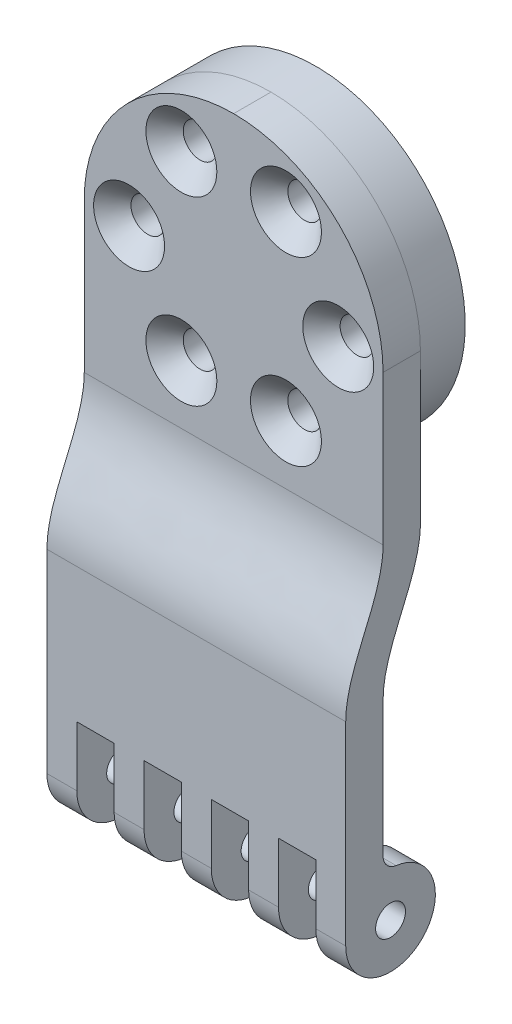
SolidWorks part; units mm, degrees
other "Markup1"
sketch "Sketch13" plane through (20, -53, 11) normal (0.0614, -0.6805, 0.7302) x (0.9699, -0.1321, -0.2046)
ref_plane "Front Plane" through (0, 0, 0) normal (0, 0, 1) x (1, 0, 0)
ref_plane "Top Plane" through (0, 0, 0) normal (0, 1, 0) x (1, 0, 0)
ref_plane "Right Plane" through (0, 0, 0) normal (1, 0, 0) x (0, 0, -1)
sketch "Sketch7" plane through (0, 0, 0) normal (0, 0, 1) x (1, 0, 0)
  line L1 (-20, 20) -> (20, 20)
  line L2 (-20, 20) -> (-20, -20)
  line L3 (-20, -20) -> (20, -20)
  line L4 (20, 20) -> (20, -20)
  line L5 (-20, 20) -> (20, -20) construction
  line L6 (-20, -20) -> (20, 20) construction
  point P0 (0, 0)
extrude "Boss-Extrude1" add sketch "Sketch7" along normal blind 11
ref_plane "Plane2" through (0, -21.4103, 5.7369) normal (0, -0.9659, 0.2588) x (1, 0, 0)
sketch "Sketch8" plane through (0, -20, 2.0782) normal (0, -1, 0) x (1, 0, 0)
  line L0 (20, 8.9218) -> (20, -2.0782) construction
  line L1 (-20, 8.9218) -> (20, 8.9218)
  line L2 (-20, 8.9218) -> (-20, 3.9218)
  line L3 (-20, 3.9218) -> (20, 3.9218)
  line L4 (20, 8.9218) -> (20, 3.9218)
  line L5 (0, 3.9218) -> (0, 8.9218) construction
  line L6 (-20, 6.4218) -> (20, 6.4218) construction
  line L7 (-20, -2.0782) -> (20, -2.0782) construction
  point P764 (0, 6.4218)
  dimension "D1" = 6
ref_plane "Plane4" through (0, -38, 0) normal (0, -1, 0) x (-1, 0, 0)
sketch "Sketch19" plane through (0, -38, 0) normal (0, -1, 0) x (-1, 0, 0)
  line L0 (20, -11) -> (20, 0) construction
  line L1 (20, -16) -> (-20, -16)
  line L2 (20, -16) -> (20, -11)
  line L3 (20, -11) -> (-20, -11)
  line L4 (-20, -16) -> (-20, -11)
  line L5 (20, -16) -> (-20, -11) construction
  line L6 (20, -11) -> (-20, -16) construction
  line L7 (-20, -11) -> (-20, 0) construction
  line L8 (20, -11) -> (-20, -11) construction
  point P4 (0, -13.5)
  dimension "D1" = 5
  dimension "D2" = 5
loft "Loft1" add profiles "Sketch19", "Sketch8" start constraint normal to profile start tangent length 1 end constraint normal to profile end tangent length 1 connector at (-20, -38, 16) connector at (-20, -20, 11)
sketch "Sketch16" plane through (0, 0, 0) normal (0, 0, -1) x (-1, 0, 0)
  line L1 (24.5131, 32.6211) -> (-24.5131, 32.6211)
  line L2 (24.5131, 32.6211) -> (24.5131, -32.6211)
  line L3 (24.5131, -32.6211) -> (-24.5131, -32.6211)
  line L4 (-24.5131, 32.6211) -> (-24.5131, -32.6211)
  line L5 (24.5131, 32.6211) -> (-24.5131, -32.6211) construction
  line L6 (24.5131, -32.6211) -> (-24.5131, 32.6211) construction
  circle A0 centre (0, 0) radius 20
extrude "Cut-Extrude3" cut sketch "Sketch16" against normal blind 6
ref_plane "Plane3" [suppressed] through (0, -56, 0) normal (0, -1, 0) x (-1, 0, 0)
sketch "Sketch17" plane through (0, -38, 0) normal (0, -1, 0) x (-1, 0, 0)
  line L1 (20, -16) -> (-20, -16)
  line L2 (20, -16) -> (20, -11)
  line L3 (20, -11) -> (-20, -11)
  line L4 (-20, -16) -> (-20, -11)
  line L5 (20, -16) -> (-20, -11) construction
  line L6 (20, -11) -> (-20, -16) construction
  line L10 (-20, -16) -> (20, -16) construction
  line L11 (-20, -6) -> (-20, -11) construction
  line L12 (20, -11) -> (20, -6) construction
  point P4 (0, -13.5)
  dimension "D1" = 5
extrude "Boss-Extrude5" add sketch "Sketch17" along normal blind 18
sketch "Sketch10" plane through (0, 0, 11) normal (0, 0, 1) x (1, 0, 0)
  circle A0 centre (-7.0001, 12.1244) radius 2.25
  circle A1 centre (6.9999, 12.1244) radius 2.25
  circle A2 centre (13.9999, 0.0001) radius 2.25
  circle A3 centre (6.9999, -12.1243) radius 2.25
  circle A4 centre (-7.0001, -12.1243) radius 2.25
  circle A5 centre (-14.0001, 0.0001) radius 2.25
  point P0 (0, 0)
  point P1 (0.0025, 0.0011)
  dimension "D4" = 4.5
extrude "Cut-Extrude1" cut sketch "Sketch10" against normal blind 25
sketch "Sketch11" plane through (0, -56, -3.473) normal (0, 1, 0) x (1, 0, 0)
  line L1 (-20, -14.473) -> (-16, -14.473)
  line L2 (-20, -14.473) -> (-20, -19.473)
  line L3 (-20, -19.473) -> (-16, -19.473)
  line L4 (-16, -14.473) -> (-16, -19.473)
  line L5 (-18, -19.473) -> (-18, -14.473) construction
  line L6 (-20, -16.973) -> (-16, -16.973) construction
  line L11 (-20, -14.473) -> (20, -14.473) construction
  line L12 (-20, -14.473) -> (-20, -9.473) construction
  line L13 (20, -19.473) -> (-20, -19.473) construction
  point P368 (-18, -16.973)
  dimension "D1" = 4
extrude "Boss-Extrude3" add sketch "Sketch11" against normal blind 8 contours L1 L4 L3 L2
ref_plane "Plane1" through (-16, 0, 0) normal (1, 0, 0) x (0, 0, -1)
sketch "Sketch14" plane through (-16, 0, 0) normal (1, 0, 0) x (0, 0, -1)
  line L0 (-16, -64) -> (-11, -64) construction
  line L7 (-16, -64) -> (-16, -38) construction
  circle A0 centre (-10, -64) radius 6
  point P2 (-10.8167, -64)
  point P3 (-9.5073, -64)
  dimension "D3" = 12
  dimension "D1" = 0
extrude "Boss-Extrude4" add sketch "Sketch14" against normal up to vertex (4 mm away) up to point (-20, -20, 11)
pattern_linear "LPattern1" count 5 spacing 9 along (1, 0, 0) of "Boss-Extrude4", "Boss-Extrude3"
sketch "Sketch15" plane through (-20, 0, 0) normal (-1, 0, 0) x (0, 0, 1)
  circle A0 centre (10, -64) radius 2
extrude "Cut-Extrude2" cut sketch "Sketch15" against normal through all
chamfer "Chamfer1" distance 2.5 angle 45 6 edges at (-4.7501, 12.1244, 11) (-11.7501, 0.0001, 11) (-4.7501, -12.1243, 11) (9.2499, 12.1244, 11) (16.2499, 0.0001, 11) (9.2499, -12.1243, 11)
fillet "Fillet2" radius 2 5 edges at (-18, -58.0839, 11) (-9, -58.0839, 11) (0, -58.0839, 11) (9, -58.0839, 11) (18, -58.0839, 11)
fillet "Fillet3" radius 20 2 edges at (20, 20, 8.5) (-20, 20, 8.5)
